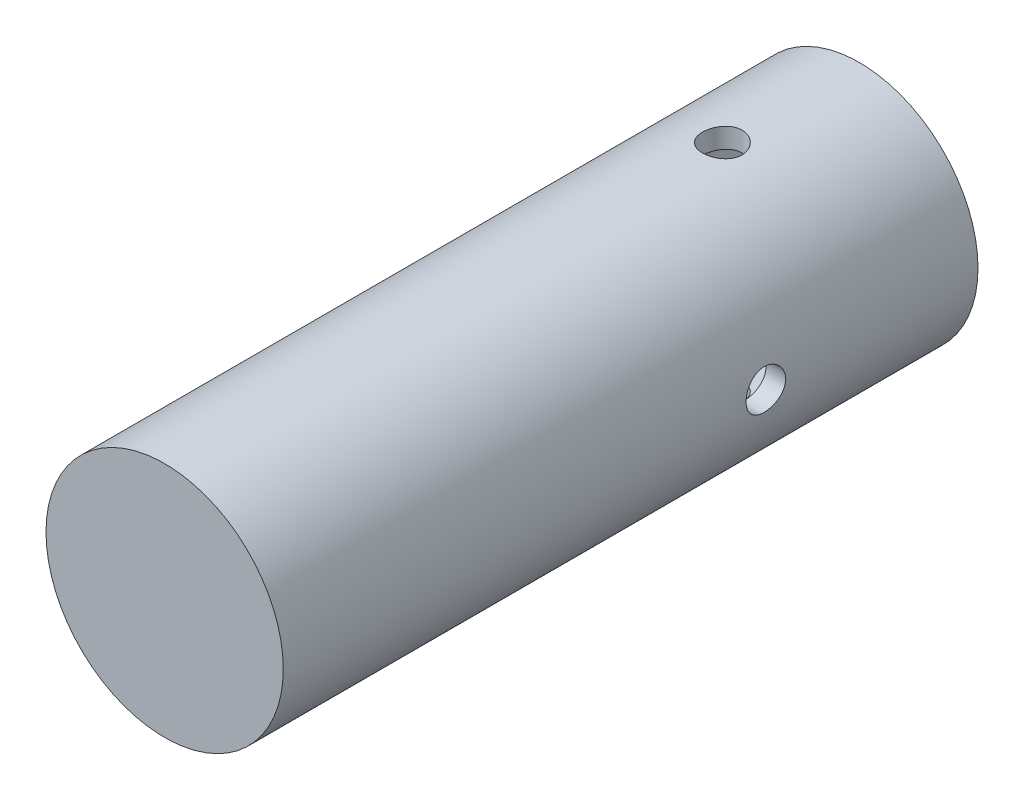
SolidWorks part; units mm, degrees
material "Hexcel AS4C (3000 Filaments)"
ref_plane "X-Y Datum" through (0, 0, 0) normal (0, 0, 1) x (1, 0, 0)
ref_plane "X-Z Datum" through (0, 0, 0) normal (0, 1, 0) x (1, 0, 0)
ref_plane "Y-Z Datum" through (0, 0, 0) normal (1, 0, 0) x (0, 0, -1)
sketch "Sketch9" plane through (0, 0, 0) normal (0, 1, 0) x (1, 0, 0)
  line L0 (16.002, 0) -> (0, 0)
  line L1 (0, 0) -> (0, -389.0916)
  line L2 (0, -389.0916) -> (-72.2493, -524.9728)
  dimension "D1" = 153.895
  dimension "D2" = 28
  dimension "D3" = 389.0916
  dimension "D5" = 16.002
sketch "Sketch5" plane through (0, 0, 0) normal (0, 1, 0) x (1, 0, 0)
  line L0 (7.9375, -77.9416) -> (7.9375, -22.1615)
  line L1 (7.9375, -22.1615) -> (9.525, -22.1615)
  line L2 (9.525, -22.1615) -> (9.525, -77.9416)
  line L3 (9.525, -77.9416) -> (7.9375, -77.9416)
  line L5 (16.002, 0) -> (0, 0) construction
  line L6 (0, 0) -> (0, -389.0916) construction
  line L7 (0, -389.0916) -> (9.525, -389.0916) construction
  line L8 (12.5602, -58.6916) -> (0, -58.6916) construction
  dimension "D1" = 1.5875
  dimension "D2" = 22.1615
  dimension "D3" = 7.9375
  dimension "D4" = 330.4
  dimension "D5" = 311.15
revolve "Revolve2" add sketch "Sketch5" angle 360 about L1
sketch "Sketch6" plane through (0, 0, 0) normal (0, 1, 0) x (1, 0, 0)
  circle A0 centre (0, -33.1635) radius 1.5875 construction
  circle A1 centre (0, -33.1635) radius 1.5875
sketch "Sketch7" plane through (0, 0, 0) normal (1, 0, 0) x (0, 0, -1)
  circle A2 centre (-39.196, 0) radius 1.5875
  circle A4 centre (-39.196, 0) radius 1.5875 construction
extrude "Cut-Extrude5" cut sketch "Sketch7" against normal through all both and the other way through all
extrude "Cut-Extrude6" cut sketch "Sketch6" against normal through all both and the other way through all
sketch "Sketch8" plane through (0, 0, 0) normal (0, 0, 1) x (1, 0, 0)
  line L0 (9.2357, -0.808) -> (8.6817, -0.254)
  line L1 (8.6817, -0.254) -> (8.6817, 0.254)
  line L2 (8.6817, 0.254) -> (9.2357, 0.808)
  line L3 (8.6817, 0) -> (0, 0) construction
  line L4 (8.9551, -2.3995) -> (8.5057, -1.7577)
  line L5 (8.5057, -1.7577) -> (8.5939, -1.2574)
  line L6 (8.5939, -1.2574) -> (9.2357, -0.808)
  line L7 (8.4024, -3.9181) -> (8.0713, -3.208)
  line L8 (8.0713, -3.208) -> (8.245, -2.7306)
  line L9 (8.245, -2.7306) -> (8.9551, -2.3995)
  line L10 (7.5944, -5.3176) -> (7.3916, -4.5608)
  line L11 (7.3916, -4.5608) -> (7.6456, -4.1209)
  line L12 (7.6456, -4.1209) -> (8.4024, -3.9181)
  line L13 (6.5556, -6.5556) -> (6.4873, -5.7751)
  line L14 (6.4873, -5.7751) -> (6.8138, -5.3859)
  line L15 (6.8138, -5.3859) -> (7.5944, -5.3176)
  line L16 (5.3176, -7.5944) -> (5.3859, -6.8138)
  line L17 (5.3859, -6.8138) -> (5.7751, -6.4873)
  line L18 (5.7751, -6.4873) -> (6.5556, -6.5556)
  line L19 (3.9181, -8.4024) -> (4.1209, -7.6456)
  line L20 (4.1209, -7.6456) -> (4.5608, -7.3916)
  line L21 (4.5608, -7.3916) -> (5.3176, -7.5944)
  line L22 (2.3995, -8.9551) -> (2.7306, -8.245)
  line L23 (2.7306, -8.245) -> (3.208, -8.0713)
  line L24 (3.208, -8.0713) -> (3.9181, -8.4024)
  line L25 (0.808, -9.2357) -> (1.2574, -8.5939)
  line L26 (1.2574, -8.5939) -> (1.7577, -8.5057)
  line L27 (1.7577, -8.5057) -> (2.3995, -8.9551)
  line L28 (-0.808, -9.2357) -> (-0.254, -8.6817)
  line L29 (-0.254, -8.6817) -> (0.254, -8.6817)
  line L30 (0.254, -8.6817) -> (0.808, -9.2357)
  line L31 (-2.3995, -8.9551) -> (-1.7577, -8.5057)
  line L32 (-1.7577, -8.5057) -> (-1.2574, -8.5939)
  line L33 (-1.2574, -8.5939) -> (-0.808, -9.2357)
  line L34 (-3.9181, -8.4024) -> (-3.208, -8.0713)
  line L35 (-3.208, -8.0713) -> (-2.7306, -8.245)
  line L36 (-2.7306, -8.245) -> (-2.3995, -8.9551)
  line L37 (-5.3176, -7.5944) -> (-4.5608, -7.3916)
  line L38 (-4.5608, -7.3916) -> (-4.1209, -7.6456)
  line L39 (-4.1209, -7.6456) -> (-3.9181, -8.4024)
  line L40 (-6.5556, -6.5556) -> (-5.7751, -6.4873)
  line L41 (-5.7751, -6.4873) -> (-5.3859, -6.8138)
  line L42 (-5.3859, -6.8138) -> (-5.3176, -7.5944)
  line L43 (-7.5944, -5.3176) -> (-6.8138, -5.3859)
  line L44 (-6.8138, -5.3859) -> (-6.4873, -5.7751)
  line L45 (-6.4873, -5.7751) -> (-6.5556, -6.5556)
  line L46 (-8.4024, -3.9181) -> (-7.6456, -4.1209)
  line L47 (-7.6456, -4.1209) -> (-7.3916, -4.5608)
  line L48 (-7.3916, -4.5608) -> (-7.5944, -5.3176)
  line L49 (-8.9551, -2.3995) -> (-8.245, -2.7306)
  line L50 (-8.245, -2.7306) -> (-8.0713, -3.208)
  line L51 (-8.0713, -3.208) -> (-8.4024, -3.9181)
  line L52 (-9.2357, -0.808) -> (-8.5939, -1.2574)
  line L53 (-8.5939, -1.2574) -> (-8.5057, -1.7577)
  line L54 (-8.5057, -1.7577) -> (-8.9551, -2.3995)
  line L55 (-9.2357, 0.808) -> (-8.6817, 0.254)
  line L56 (-8.6817, 0.254) -> (-8.6817, -0.254)
  line L57 (-8.6817, -0.254) -> (-9.2357, -0.808)
  line L58 (-8.9551, 2.3995) -> (-8.5057, 1.7577)
  line L59 (-8.5057, 1.7577) -> (-8.5939, 1.2574)
  line L60 (-8.5939, 1.2574) -> (-9.2357, 0.808)
  line L61 (-8.4024, 3.9181) -> (-8.0713, 3.208)
  line L62 (-8.0713, 3.208) -> (-8.245, 2.7306)
  line L63 (-8.245, 2.7306) -> (-8.9551, 2.3995)
  line L64 (-7.5944, 5.3176) -> (-7.3916, 4.5608)
  line L65 (-7.3916, 4.5608) -> (-7.6456, 4.1209)
  line L66 (-7.6456, 4.1209) -> (-8.4024, 3.9181)
  line L67 (-6.5556, 6.5556) -> (-6.4873, 5.7751)
  line L68 (-6.4873, 5.7751) -> (-6.8138, 5.3859)
  line L69 (-6.8138, 5.3859) -> (-7.5944, 5.3176)
  line L70 (-5.3176, 7.5944) -> (-5.3859, 6.8138)
  line L71 (-5.3859, 6.8138) -> (-5.7751, 6.4873)
  line L72 (-5.7751, 6.4873) -> (-6.5556, 6.5556)
  line L73 (-3.9181, 8.4024) -> (-4.1209, 7.6456)
  line L74 (-4.1209, 7.6456) -> (-4.5608, 7.3916)
  line L75 (-4.5608, 7.3916) -> (-5.3176, 7.5944)
  line L76 (-2.3995, 8.9551) -> (-2.7306, 8.245)
  line L77 (-2.7306, 8.245) -> (-3.208, 8.0713)
  line L78 (-3.208, 8.0713) -> (-3.9181, 8.4024)
  line L79 (-0.808, 9.2357) -> (-1.2574, 8.5939)
  line L80 (-1.2574, 8.5939) -> (-1.7577, 8.5057)
  line L81 (-1.7577, 8.5057) -> (-2.3995, 8.9551)
  line L82 (0.808, 9.2357) -> (0.254, 8.6817)
  line L83 (0.254, 8.6817) -> (-0.254, 8.6817)
  line L84 (-0.254, 8.6817) -> (-0.808, 9.2357)
  line L85 (2.3995, 8.9551) -> (1.7577, 8.5057)
  line L86 (1.7577, 8.5057) -> (1.2574, 8.5939)
  line L87 (1.2574, 8.5939) -> (0.808, 9.2357)
  line L88 (3.9181, 8.4024) -> (3.208, 8.0713)
  line L89 (3.208, 8.0713) -> (2.7306, 8.245)
  line L90 (2.7306, 8.245) -> (2.3995, 8.9551)
  line L91 (5.3176, 7.5944) -> (4.5608, 7.3916)
  line L92 (4.5608, 7.3916) -> (4.1209, 7.6456)
  line L93 (4.1209, 7.6456) -> (3.9181, 8.4024)
  line L94 (6.5556, 6.5556) -> (5.7751, 6.4873)
  line L95 (5.7751, 6.4873) -> (5.3859, 6.8138)
  line L96 (5.3859, 6.8138) -> (5.3176, 7.5944)
  line L97 (7.5944, 5.3176) -> (6.8138, 5.3859)
  line L98 (6.8138, 5.3859) -> (6.4873, 5.7751)
  line L99 (6.4873, 5.7751) -> (6.5556, 6.5556)
  line L100 (8.4024, 3.9181) -> (7.6456, 4.1209)
  line L101 (7.6456, 4.1209) -> (7.3916, 4.5608)
  line L102 (7.3916, 4.5608) -> (7.5944, 5.3176)
  line L103 (8.9551, 2.3995) -> (8.245, 2.7306)
  line L104 (8.245, 2.7306) -> (8.0713, 3.208)
  line L105 (8.0713, 3.208) -> (8.4024, 3.9181)
  line L106 (9.2357, 0.808) -> (8.5939, 1.2574)
  line L107 (8.5939, 1.2574) -> (8.5057, 1.7577)
  line L108 (8.5057, 1.7577) -> (8.9551, 2.3995)
  circle A0 centre (0, 0) radius 12.7
  circle A1 centre (0, 0) radius 9.271 construction
  circle A2 centre (0, 0) radius 8.6854 construction
  point P153 (0, 0)
  dimension "D1" = 25.4
  dimension "D4" = 18.542
  dimension "D6" = 17.3708
  dimension "D2" = 0.508
  dimension "D3" = 135
  dimension "D5" = 36
ref_plane "Plane1" through (0, 0, 47.5615) normal (0, 0, -1) x (-1, 0, 0)
sketch "Sketch10" plane through (0, 0, 47.5615) normal (0, 0, -1) x (-1, 0, 0)
  circle A0 centre (0, 0) radius 7.9375
  dimension "D1" = 15.875
extrude "Boss-Extrude1" add sketch "Sketch10" against normal up to surface (30.3801 mm away) up to face at (-9.525, 0, 77.9416)
sketch "Sketch11" plane through (0, 0, 22.1615) normal (0, 0, -1) x (-1, 0, 0)
  line L0 (0, 9.525) -> (13.3548, 9.525) construction
  line L1 (0, 9.525) -> (0, 15.4312) construction
  line L2 (-9.525, 0) -> (-9.525, 9.1744) construction
  line L3 (-9.525, 0) -> (-16.674, 0) construction
  circle A0 centre (0, 0) radius 9.525 construction
  point P0 (0, 9.525)
  point P1 (-9.525, 0)
